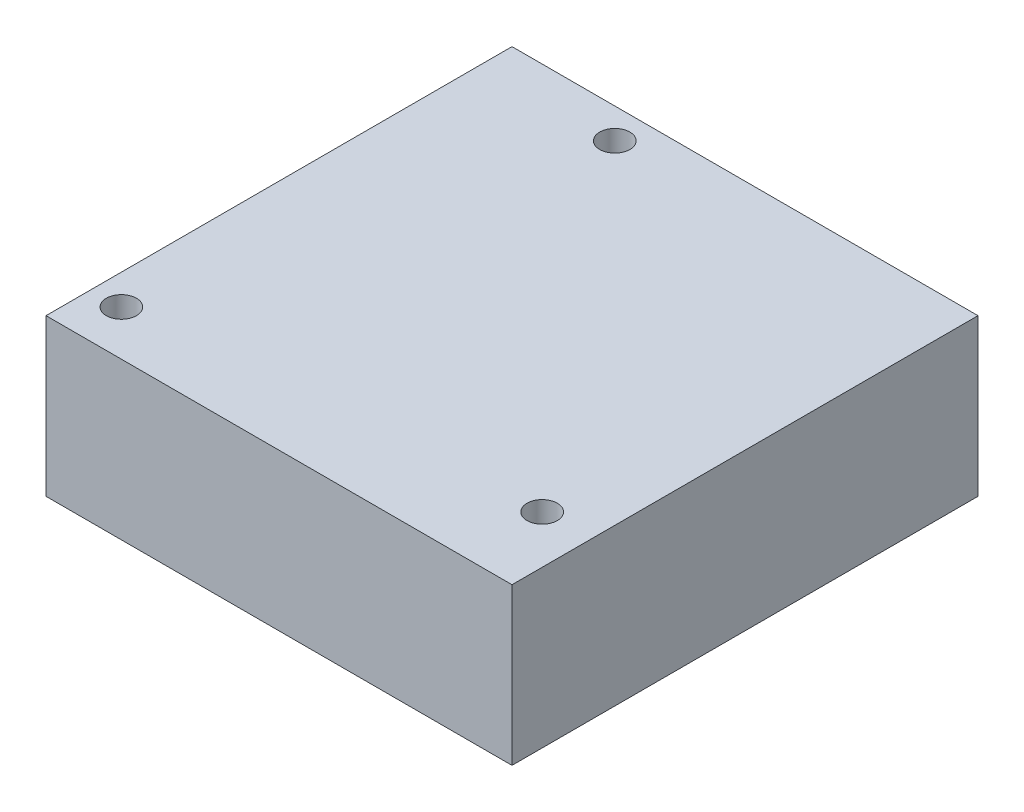
SolidWorks part; units mm, degrees
material "1060 Alloy"
ref_plane "Front Plane" through (0, 0, 0) normal (0, 0, 1) x (1, 0, 0)
ref_plane "Top Plane" through (0, 0, 0) normal (0, 1, 0) x (1, 0, 0)
ref_plane "Right Plane" through (0, 0, 0) normal (1, 0, 0) x (0, 0, -1)
sketch "Sketch1" plane through (0, 0, 0) normal (0, 1, 0) x (1, 0, 0)
  line L1 (21.59, 21.59) -> (-21.59, 21.59)
  line L2 (21.59, 21.59) -> (21.59, -21.59)
  line L3 (21.59, -21.59) -> (-21.59, -21.59)
  line L4 (-21.59, 21.59) -> (-21.59, -21.59)
  line L5 (21.59, 21.59) -> (-21.59, -21.59) construction
  line L6 (21.59, -21.59) -> (-21.59, 21.59) construction
  point P0 (0, 0)
  dimension "D1" = 43.18
  dimension "D2" = 43.18
extrude "Boss-Extrude1" add sketch "Sketch1" along normal blind 15 contours L4 L3 L2 L1
hole_wizard "M3 Clearance Hole1" positions "Sketch3" profile "Sketch2" hole size "M3" standard "ANSI Metric" end condition through all
sketch "Sketch3" plane through (0, 15, 0) normal (0, 1, 0) x (1, 0, 0)
  line L0 (-21.59, 21.59) -> (-21.59, -21.59) construction
  line L1 (21.59, -21.59) -> (-21.59, -21.59) construction
  point P0 (-18.796, -17.399)
  point P2 (-9.271, 18.796)
  point P4 (17.145, -14.351)
  dimension "D1" = 2.794
  dimension "D2" = 4.191
  dimension "D3" = 12.319
  dimension "D4" = 40.386
  dimension "D5" = 38.735
  dimension "D6" = 7.239
sketch "Sketch2" plane through (-18.796, 15, 17.399) normal (1, 0, 0) x (0, 0, 1)
  line L0 (0, 0) -> (0, 15)
  line L1 (0, 15) -> (1.4, 15)
  line L2 (1.4, 15) -> (1.4, 0)
  line L5 (1.4, 0) -> (0, 0)
  line L11 (0, -6.35) -> (0, 107.95) construction
  dimension "Thru Hole Dia." = 2.8
  dimension "Thru Hole Depth" = 15
chamfer "Chamfer1" distance 0.5 angle 45 4 edges at (0, 0, 21.59) (-21.59, 0, 0) (21.59, 0, 0) (0, 0, -21.59)
